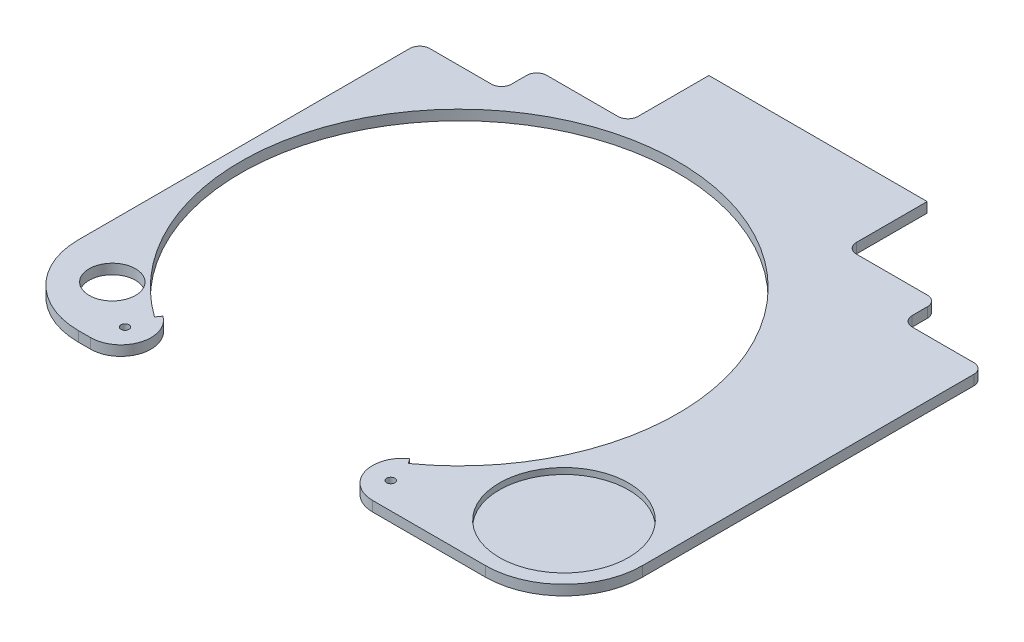
SolidWorks part; units mm, degrees
material "ABS PC"
ref_plane "Plan de face" through (0, 0, 0) normal (0, 0, 1) x (1, 0, 0)
ref_plane "Plan de dessus" through (0, 0, 0) normal (0, 1, 0) x (1, 0, 0)
ref_plane "Plan de droite" through (0, 0, 0) normal (1, 0, 0) x (0, 0, -1)
sketch "Esquisse1" plane through (0, 0, 0) normal (0, 1, 0) x (1, 0, 0)
  line L1 (-140.1, 31.2) -> (140.1, 31.2)
  line L2 (-140.1, 31.2) -> (-140.1, -245.0829)
  line L3 (-140.1, -245.0829) -> (140.1, -245.0829)
  line L4 (140.1, 31.2) -> (140.1, -245.0829)
  line L8 (-84, 31.2) -> (84, 31.2) construction
  line L9 (-140.1, 4) -> (-140.1, -4) construction
  line L10 (140.1, -4) -> (140.1, 4) construction
  line L11 (-95, -245.0829) -> (-100, -245.0829) construction
extrude "Boss.-Extru.1" add sketch "Esquisse1" along normal blind 5
sketch "Esquisse2" plane through (0, 5, 0) normal (0, 1, 0) x (1, 0, 0)
  line L0 (-86.2863, -217.8734) -> (-88.029, -220.3153) construction
  line L2 (-86.2863, -217.8734) -> (-88.029, -220.3153)
  line L3 (45, -245.0829) -> (-95, -245.0829)
  line L4 (36.2863, -217.8734) -> (38.029, -220.3153) construction
  line L5 (36.2863, -217.8734) -> (38.029, -220.3153)
  arc A1 (-95, -245.0829) -> (-86.2863, -217.8734) centre (-95, -230.0829) ccw construction
  arc A2 (-25, -23.5) -> (-88.029, -220.3153) centre (-25, -132) ccw construction
  arc A3 (-25, -23.5) -> (-88.029, -220.3153) centre (-25, -132) ccw
  arc A4 (-95, -245.0829) -> (-86.2863, -217.8734) centre (-95, -230.0829) ccw
  arc A5 (36.2863, -217.8734) -> (45, -245.0829) centre (45, -230.0829) ccw construction
  arc A6 (36.2863, -217.8734) -> (45, -245.0829) centre (45, -230.0829) ccw
  arc A7 (38.029, -220.3153) -> (-25, -23.5) centre (-25, -132) ccw
extrude "Enlèv. mat.-Extru.1" cut sketch "Esquisse2" against normal through all
sketch "Esquisse3" plane through (0, 5, 0) normal (0, 1, 0) x (1, 0, 0)
  arc A1 (89.8611, -236.1424) -> (112.3389, -176.0233) centre (101.1, -206.0829) ccw
  arc A2 (90.5615, -234.2691) -> (111.6385, -177.8967) centre (101.1, -206.0829) ccw
  arc A3 (90.5615, -234.2691) -> (111.6385, -177.8967) centre (101.1, -206.0829) ccw construction
  arc A4 (111.6385, -177.8967) -> (90.5615, -234.2691) centre (101.1, -206.0829) ccw
  arc A5 (111.6385, -177.8967) -> (90.5615, -234.2691) centre (101.1, -206.0829) ccw construction
  arc A6 (112.3389, -176.0233) -> (89.8611, -236.1424) centre (101.1, -206.0829) ccw
  dimension "D1" = 2
sketch "Esquisse4" plane through (0, 5, 0) normal (0, 1, 0) x (1, 0, 0)
  line L0 (140.1, -245.0829) -> (101.1, -245.0829)
  line L1 (140.1, -245.0829) -> (140.1, -206.0829)
  line L2 (-101.1, -245.0829) -> (-140.1, -245.0829)
  line L3 (-140.1, -245.0829) -> (-140.1, -206.0829)
  arc A0 (101.1, -245.0829) -> (140.1, -206.0829) centre (101.1, -206.0829) ccw construction
  arc A1 (101.1, -245.0829) -> (140.1, -206.0829) centre (101.1, -206.0829) ccw
  arc A2 (-140.1, -206.0829) -> (-101.1, -245.0829) centre (-101.1, -206.0829) ccw construction
  arc A3 (-140.1, -206.0829) -> (-101.1, -245.0829) centre (-101.1, -206.0829) ccw
extrude "Enlèv. mat.-Extru.3" cut sketch "Esquisse4" against normal through all
sketch "Esquisse5" plane through (0, 5, 0) normal (0, 1, 0) x (1, 0, 0)
  circle A0 centre (-91, -232) radius 2 construction
  circle A1 centre (-91, -232) radius 2
  circle A2 centre (41, -232) radius 2 construction
  circle A3 centre (41, -232) radius 2
extrude "Enlèv. mat.-Extru.4" cut sketch "Esquisse5" against normal through all
sketch "Esquisse6" plane through (0, 5, 0) normal (0, 1, 0) x (1, 0, 0)
  line L0 (99.5, 0) -> (99.5, 26.9) construction
  line L1 (140.1, 31.2) -> (0, 31.2)
  line L2 (140.1, 31.2) -> (140.1, -41.5125)
  line L3 (135.1, -36.5125) -> (104.5, -36.5125)
  line L4 (99.5, -24) -> (99.5, -31.5125)
  line L5 (94.5, -19) -> (59.2094, -19)
  line L6 (54.2094, -14) -> (54.2094, 21.2)
  line L7 (54.2094, 21.2) -> (-54.2094, 21.2)
  line L8 (-85, 21.2) -> (85, 21.2) construction
  line L9 (56.2094, 14) -> (56.2094, -14) construction
  line L10 (91.7094, -16) -> (92.7094, -16) construction
  line L11 (-54.2094, -14) -> (-54.2094, 21.2)
  line L12 (-94.5, -19) -> (-59.2094, -19)
  line L13 (-99.5, -24) -> (-99.5, -31.5125)
  line L14 (120.5, -36.5125) -> (130.66, -36.5125) construction
  line L15 (-135.1, -36.5125) -> (-104.5, -36.5125)
  line L16 (-140.1, 31.2) -> (-140.1, -41.5125)
  line L17 (-140.1, 31.2) -> (0, 31.2)
  line L25 (0, 0) -> (0, 86.4947) construction
  line L27 (140.1, 36.5125) -> (140.1, -245.0829) construction
  line L36 (140.1, 31.2) -> (-140.1, 31.2) construction
  arc A0 (140.1, -41.5125) -> (135.1, -36.5125) centre (135.1, -41.5125) ccw
  arc A1 (-99.5, -24) -> (-94.5, -19) centre (-94.5, -24) cw
  arc A2 (59.2094, -19) -> (54.2094, -14) centre (59.2094, -14) cw
  arc A3 (-104.5, -36.5125) -> (-99.5, -31.5125) centre (-104.5, -31.5125) ccw
  arc A4 (104.5, -36.5125) -> (99.5, -31.5125) centre (104.5, -31.5125) cw
  arc A5 (99.5, -24) -> (94.5, -19) centre (94.5, -24) ccw
  arc A6 (-59.2094, -19) -> (-54.2094, -14) centre (-59.2094, -14) ccw
  arc A7 (-140.1, -41.5125) -> (-135.1, -36.5125) centre (-135.1, -41.5125) cw
  point P41 (99.5, -36.5125)
  point P43 (99.5, -19)
  point P49 (0, 21.2)
  dimension "D1" = 5
  dimension "D2" = 2
  dimension "D3" = 3
extrude "Enlèv. mat.-Extru.5" cut sketch "Esquisse6" against normal through all
sketch "Esquisse7" plane through (0, 5, 0) normal (0, 1, 0) x (1, 0, 0)
  circle A0 centre (-113.5, -215.8) radius 11.5 construction
  circle A1 centre (-113.5, -215.8) radius 11.5
extrude "Enlèv. mat.-Extru.6" cut sketch "Esquisse7" against normal through all
extrude "Enlèv. mat.-Extru.7" cut sketch "Esquisse3" against normal blind 3
